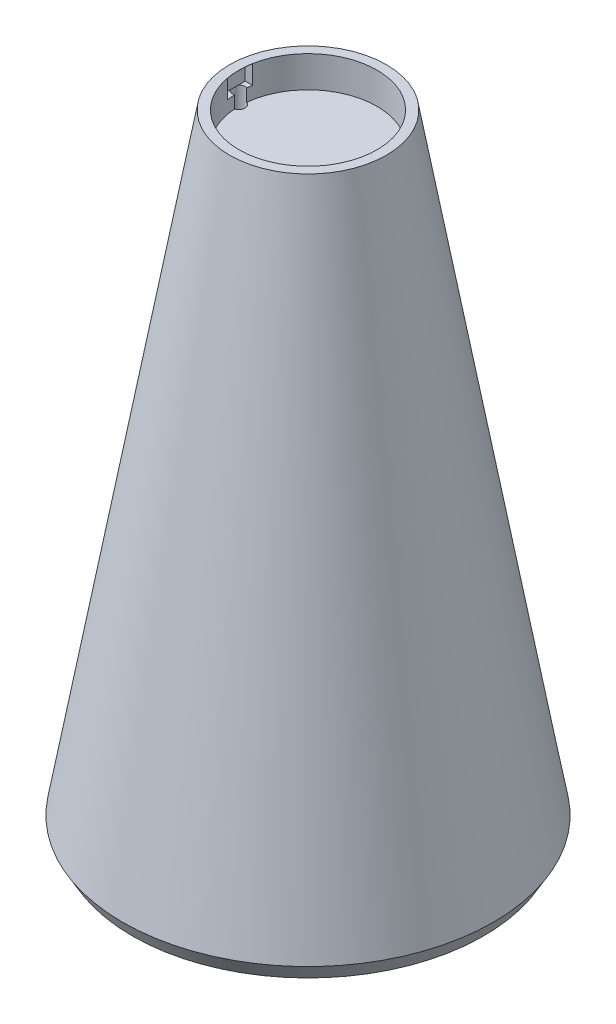
SolidWorks part; units mm, degrees
ref_plane "Front Plane" through (0, 0, 0) normal (0, 0, 1) x (1, 0, 0)
ref_plane "Top Plane" through (0, 0, 0) normal (0, 1, 0) x (1, 0, 0)
ref_plane "Right Plane" through (0, 0, 0) normal (1, 0, 0) x (0, 0, -1)
sketch "Sketch1" plane through (0, 0, 0) normal (0, 1, 0) x (1, 0, 0)
  circle A0 centre (0, 0) radius 30
  dimension "D1" = 60
ref_plane "Plane1" through (0, 100, 0) normal (0, 1, 0) x (1, 0, 0)
sketch "Sketch2" plane through (0, 100, 0) normal (0, 1, 0) x (1, 0, 0)
  circle A0 centre (0, 0) radius 12.5
  dimension "D1" = 25
loft "Loft1" add profiles "Sketch2", "Sketch1" connector at (-1.3951, 100, 12.4219) connector at (-1.4885, 0, 29.963)
sketch "Sketch5" plane through (0, 100, 0) normal (0, 1, 0) x (1, 0, 0)
  circle A0 centre (0, 0) radius 11
  dimension "D1" = 22
extrude "Cut-Extrude2" cut sketch "Sketch5" against normal blind 5
sketch "Sketch7" plane through (0, 0, 0) normal (1, 0, 0) x (0, 0, -1)
  line L1 (-2.0009, 99.9799) -> (1.9991, 99.9799)
  line L2 (-2.0009, 99.9799) -> (-2.0009, 96.9799)
  line L3 (-2.0009, 96.9799) -> (1.9991, 96.9799)
  line L4 (1.9991, 99.9799) -> (1.9991, 96.9799)
  line L5 (-2.0009, 99.9799) -> (1.9991, 96.9799) construction
  line L6 (-2.0009, 96.9799) -> (1.9991, 99.9799) construction
  point P0 (-0.0009, 98.4799)
  dimension "D1" = 3
  dimension "D2" = 4
extrude "Cut-Extrude4" cut sketch "Sketch7" against normal blind 12
sketch "Sketch8" plane through (0, 96.9799, 0) normal (0, 1, 0) x (1, 0, 0)
  circle A0 centre (-11.276, 0.2286) radius 1
  dimension "D1" = 2
shell "Shell2" thickness 2.5 removed face at (0, 0, 30)
extrude "Cut-Extrude6" cut sketch "Sketch8" against normal through all
chamfer "Chamfer1" distance 2 angle 60 1 edges at (0, 0, 30) first distance on face at (0, 0, 27.462)
